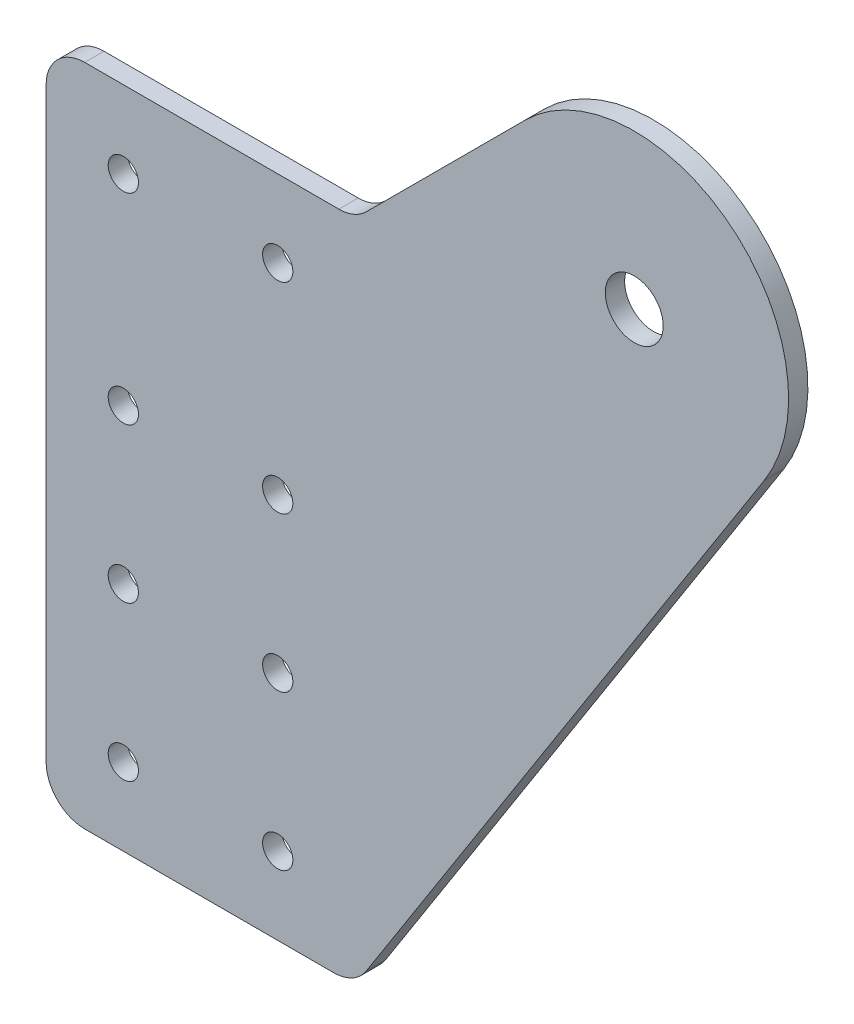
SolidWorks part; units mm, degrees
material "6061-T6 (SS)"
ref_plane "Front Plane" through (0, 0, 0) normal (0, 0, 1) x (1, 0, 0)
ref_plane "Top Plane" through (0, 0, 0) normal (0, 1, 0) x (1, 0, 0)
ref_plane "Right Plane" through (0, 0, 0) normal (1, 0, 0) x (0, 0, -1)
sketch "Sketch2" plane through (0, 0, 0) normal (0, 0, 1) x (1, 0, 0)
  line L0 (50.8, 109.22) -> (78.7932, 137.2132)
  line L1 (0, 0) -> (50.8, 0)
  line L2 (0, 0) -> (0, 109.22)
  line L3 (0, 109.22) -> (50.8, 109.22)
  line L5 (50.8, 0) -> (118.1669, 105.5912)
  arc A1 (118.1669, 105.5912) -> (78.7932, 137.2132) centre (96.7537, 119.2527) ccw
  circle A2 centre (96.7537, 119.2527) radius 4.7625
  dimension "D3" = 50.8
  dimension "D4" = 9.525
  dimension "D1" = 50.8
  dimension "D2" = 109.22
extrude "Boss-Extrude1" add sketch "Sketch2" against normal blind 3.175
sketch "Sketch3" plane through (0, 0, 0) normal (0, 0, 1) x (1, 0, 0)
  line L0 (50.8, 109.22) -> (0, 109.22) construction
  line L1 (0, 109.22) -> (0, 0) construction
  circle A0 centre (12.7, 96.52) radius 2.4892
  circle A17 centre (38.1, 96.52) radius 2.4892
  circle A24 centre (12.7, 63.5) radius 2.4892
  circle A25 centre (12.7, 38.1) radius 2.4892
  circle A26 centre (12.7, 12.7) radius 2.4892
  circle A27 centre (12.7, -12.7) radius 2.4892
  circle A28 centre (12.7, -38.1) radius 2.4892
  circle A33 centre (38.1, 38.1) radius 2.4892
  circle A34 centre (38.1, 12.7) radius 2.4892
  circle A35 centre (38.1, -12.7) radius 2.4892
  circle A36 centre (38.1, -38.1) radius 2.4892
  circle A41 centre (38.1, 63.5) radius 2.4892
  dimension "D1" = 4.9784
  dimension "D6" = 4.9784
  dimension "D2" = 12.7
  dimension "D3" = 12.7
  dimension "D7" = 12.7
  dimension "D8" = 33.02
  dimension "D4" = 1
  dimension "D5" = 2
  dimension "D9" = 5
  dimension "D10" = 2
extrude "Cut-Extrude1" cut sketch "Sketch3" against normal through all
fillet "Fillet1" radius 6.35 4 edges at (0, 0, -1.5875) (50.8, 0, -1.5875) (50.8, 109.22, -1.5875) (0, 109.22, -1.5875)
